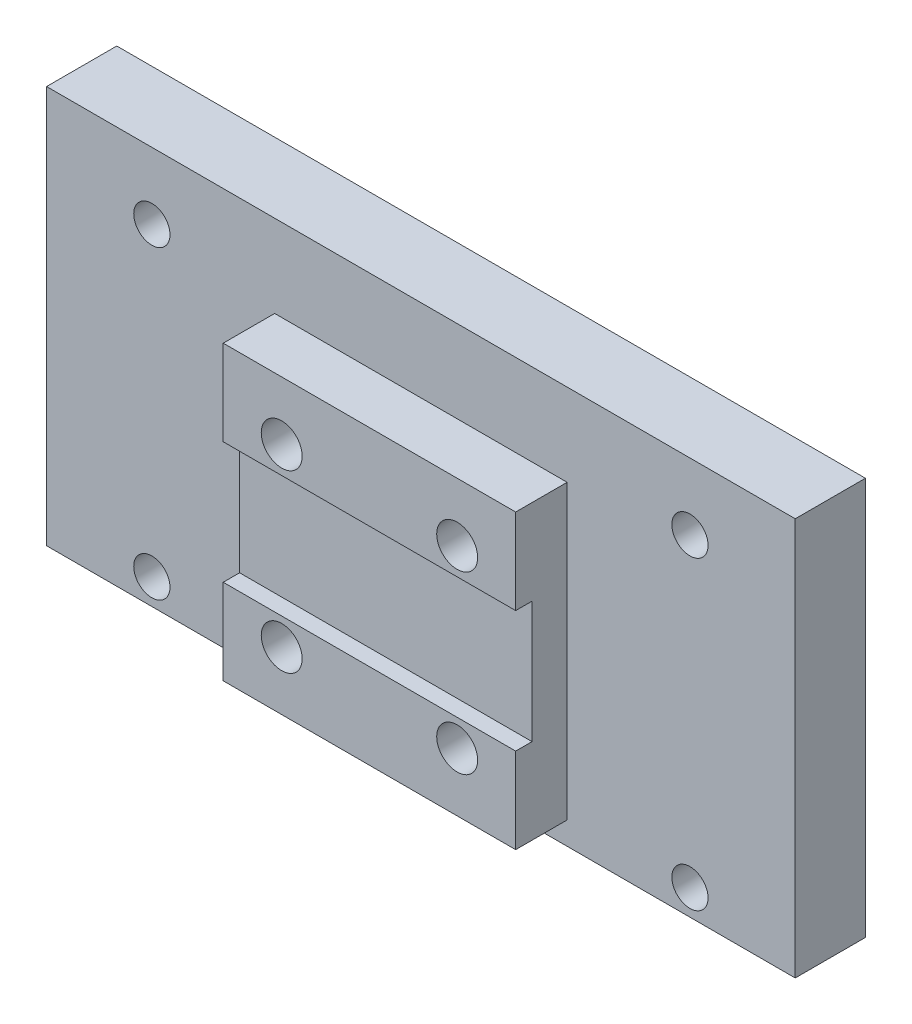
SolidWorks part; units mm, degrees
ref_plane "前视基准面" through (0, 0, 0) normal (0, 0, 1) x (1, 0, 0)
ref_plane "上视基准面" through (0, 0, 0) normal (0, 1, 0) x (1, 0, 0)
ref_plane "右视基准面" through (0, 0, 0) normal (1, 0, 0) x (0, 0, -1)
other "Configuration Table"
sketch "草图1" plane through (0, 0, 0) normal (0, 0, 1) x (1, 0, 0)
  line L5 (0, 0) -> (25, 0)
  line L6 (0, 0) -> (0, 25)
  line L7 (0, 25) -> (25, 25)
  line L8 (25, 0) -> (25, 25)
  line L9 (5, 20) -> (20, 20) construction
  line L10 (5, 20) -> (5, 5) construction
  line L11 (5, 5) -> (20, 5) construction
  line L12 (20, 20) -> (20, 5) construction
  circle A0 centre (5, 20) radius 1.75
  circle A1 centre (20, 20) radius 1.75
  circle A2 centre (5, 5) radius 1.75
  circle A3 centre (20, 5) radius 1.75
  dimension "D4" = 3.5
  dimension "D1" = 25
  dimension "D2" = 25
  dimension "D3" = 15
  dimension "D5" = 5
  dimension "D6" = 5
  dimension "D7" = 15
extrude "凸台-拉伸1" add sketch "草图1" along normal blind 3
sketch "草图2" plane through (0, 0, 3) normal (0, 0, 1) x (1, 0, 0)
  line L0 (0, 17.7) -> (25, 17.7)
  line L1 (0, 25) -> (0, 0) construction
  line L2 (25, 0) -> (25, 25) construction
  line L4 (25, 7.3) -> (0, 7.3)
  line L6 (0, 7.3) -> (0, 0)
  line L7 (25, 17.7) -> (25, 25)
  line L10 (0, 25) -> (0, 0)
  line L11 (0, 0) -> (25, 0)
  line L12 (25, 0) -> (25, 25)
  line L13 (25, 25) -> (0, 25)
  line L14 (0, 25) -> (0, 17.7)
  line L15 (0, 0) -> (25, 0)
  line L16 (25, 0) -> (25, 7.3)
  line L17 (25, 25) -> (0, 25)
  dimension "D1" = 0
  dimension "D2" = 10.4
  dimension "D3" = 7.3
extrude "凸台-拉伸2" add sketch "草图2" along normal blind 1.4
sketch "草图3" plane through (0, 0, 4.4) normal (0, 0, 1) x (1, 0, 0)
  circle A0 centre (5, 5) radius 1.75 construction
  circle A1 centre (20, 5) radius 1.75 construction
  circle A2 centre (20, 20) radius 1.75 construction
  circle A3 centre (5, 20) radius 1.75 construction
  circle A4 centre (5, 5) radius 1.75
  circle A5 centre (20, 5) radius 1.75
  circle A6 centre (20, 20) radius 1.75
  circle A7 centre (5, 20) radius 1.75
extrude "切除-拉伸1" cut sketch "草图3" against normal through all
sketch "草图6" plane through (0, 0, 0) normal (0, 0, -1) x (-1, 0, 0)
  line L0 (0, 25) -> (0, 0) construction
  line L1 (-42.5, 28.05) -> (17.5, 28.05) construction
  line L2 (-42.5, 28.05) -> (-42.5, -3.05) construction
  line L3 (-42.5, -3.05) -> (17.5, -3.05) construction
  line L4 (17.5, 28.05) -> (17.5, -3.05) construction
  line L6 (0, 0) -> (-25, 0) construction
  line L7 (10.5, 2.45) -> (-35.5, 2.45) construction
  line L8 (-35.5, 2.45) -> (-35.5, 22.55) construction
  line L9 (-35.5, 22.55) -> (10.5, 22.55) construction
  line L10 (10.5, 22.55) -> (10.5, 2.45) construction
  line L12 (-44.5, 32.05) -> (19.5, 32.05)
  line L13 (-44.5, 32.05) -> (-44.5, -4.05)
  line L14 (-44.5, -4.05) -> (19.5, -4.05)
  line L15 (19.5, 32.05) -> (19.5, -4.05)
  dimension "D1" = 60
  dimension "D2" = 31.1
  dimension "D3" = 17.5
  dimension "D4" = 3.05
  dimension "D5" = 7
  dimension "D6" = 5.5
  dimension "D8" = 7
  dimension "D9" = 5.5
  dimension "D10" = 2
  dimension "D11" = 4
  dimension "D12" = 2
  dimension "D13" = 1
extrude "凸台-拉伸5" add sketch "草图6" along normal blind 6
sketch "草图7" plane through (0, 0, -6) normal (0, 0, -1) x (-1, 0, 0)
  line L0 (-25, 3) -> (0, 3)
  line L4 (-25, 0) -> (0, 0)
  line L5 (-25, 25) -> (-25, 0)
  line L6 (0, 25) -> (-25, 25)
  line L7 (0, 0) -> (0, 25)
  line L9 (-25, 25) -> (-25, 3)
  line L10 (0, 25) -> (-25, 25)
  line L11 (0, 3) -> (0, 25)
  dimension "D1" = 3
  dimension "D5" = 0
extrude "切除-拉伸2" cut sketch "草图7" against normal blind 5
extrude "切除-拉伸5" cut sketch "草图3<2>" against normal through all
sketch "草图3<2>" plane through (0, 0, 4.4) normal (0, 0, 1) x (1, 0, 0) same geometry as "草图3"
sketch "草图9" plane through (0, 0, 0) normal (0, 0, 1) x (1, 0, 0)
  line L0 (-19.5, -4.05) -> (-19.5, 32.05) construction
  line L1 (-19.5, -1.95) -> (44.5, -1.95)
  line L2 (-19.5, -1.95) -> (-19.5, -4.05)
  line L3 (-19.5, -4.05) -> (44.5, -4.05)
  line L4 (44.5, -1.95) -> (44.5, -4.05)
  dimension "D1" = 2.1
extrude "切除-拉伸6" cut sketch "草图9" against normal blind 10
sketch "草图10" plane through (0, 0, -8.42) normal (0, 0, 1) x (1, 0, 0)
  circle A1 centre (-10.5, 26.35) radius 1.55
  circle A2 centre (-10.5, 26.35) radius 1.55
  circle A3 centre (35.5, 26.35) radius 1.55
  circle A4 centre (35.5, 26.35) radius 1.55
  circle A5 centre (35.5, 0.25) radius 1.55
  circle A6 centre (35.5, 0.25) radius 1.55
  circle A7 centre (-10.5, 0.25) radius 1.55
  circle A8 centre (-10.5, 0.25) radius 1.55
  dimension "D1" = 0
  dimension "D2" = 0
  dimension "D3" = 0
  dimension "D4" = 0
extrude "切除-拉伸7" cut sketch "草图10" along normal through all
